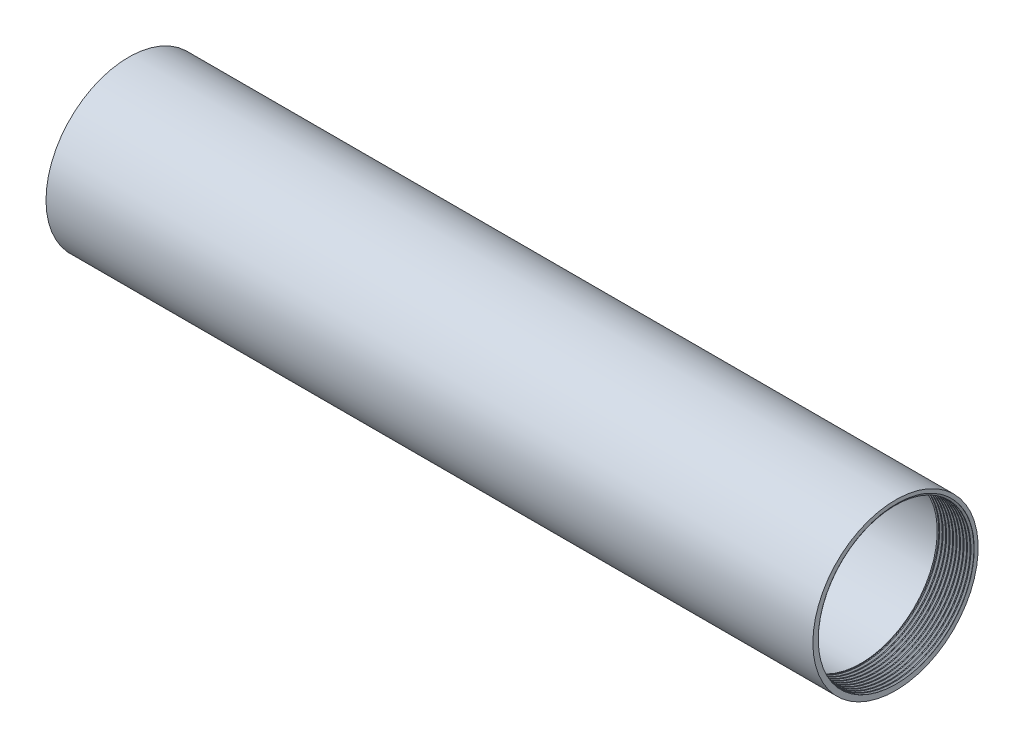
SolidWorks part; units mm, degrees
material "6061-T6 (SS)"
ref_plane "Front Plane" through (0, 0, 0) normal (0, 0, 1) x (1, 0, 0)
ref_plane "Top Plane" through (0, 0, 0) normal (0, 1, 0) x (1, 0, 0)
ref_plane "Right Plane" through (0, 0, 0) normal (1, 0, 0) x (0, 0, -1)
sketch "Sketch1" plane through (0, 0, 0) normal (0, 0, 1) x (1, 0, 0)
  line L0 (0, 37.719) -> (350.012, 37.719)
  line L1 (0, 0) -> (350.012, 0) construction
  line L2 (0, 37.719) -> (0, 35.2425)
  line L3 (0, 35.2425) -> (15.875, 35.2425)
  line L4 (15.875, 35.2425) -> (15.875, 34.925)
  line L5 (15.875, 34.925) -> (334.137, 34.925)
  line L6 (334.137, 34.925) -> (334.137, 35.2425)
  line L7 (334.137, 35.2425) -> (350.012, 35.2425)
  line L8 (350.012, 35.2425) -> (350.012, 37.719)
  point P6 (350.012, 36.4807)
  dimension "D1" = 350.012
  dimension "D2" = 34.925
  dimension "D3" = 37.719
  dimension "D4" = 35.2425
  dimension "D5" = 15.875
  dimension "D6" = 15.875
revolve "Revolve1" add sketch "Sketch1" angle 360 about L1
thread "Thread1" pitch 1.5875 method cut trim with start face yes trim with end face yes profile "Thread Profile1" start angle 0, offset 1.5875, length 0, pitch 1.5875, diameter 70.485
ref_plane "Plane1" through (17.4625, 0, 35.2425) normal (0, -1, 0) x (0, 0, 1)
sketch "Thread Profile1" plane through (17.4625, 0, 35.2425) normal (0, -1, 0) x (0, 0, 1)
  line L0 (0, 0) -> (0, 1.5875) construction
  line L1 (0, 0) -> (0.8593, 0.4961)
  line L2 (0.8593, 0.4961) -> (0.8593, 0.6945)
  line L3 (0.8593, 0.6945) -> (0, 1.1906)
  line L4 (0.8593, 0.5953) -> (0, 0.5953) construction
  line L11 (0, 0) -> (0, 1.1906)
  point P2 (0, 0)
  dimension "Pitch" = 1.5875
  dimension "Profile_Angle" = 60
  dimension "Profile_Land" = 0.1984
  dimension "Profile_Height" = 0.8593
thread "Thread2" pitch 1.5875 method cut trim with start face yes trim with end face yes profile "Thread Profile2" start angle 180, offset 1.5875, length 0, pitch 1.5875, diameter 70.485
ref_plane "Plane2" through (332.5495, 0, 35.2425) normal (0, 1, 0) x (0, 0, 1)
sketch "Thread Profile2" plane through (332.5495, 0, 35.2425) normal (0, 1, 0) x (0, 0, 1)
  line L0 (0, 0) -> (0, 1.5875) construction
  line L1 (0, 0) -> (0.8593, 0.4961)
  line L2 (0.8593, 0.4961) -> (0.8593, 0.6945)
  line L3 (0.8593, 0.6945) -> (0, 1.1906)
  line L4 (0.8593, 0.5953) -> (0, 0.5953) construction
  line L11 (0, 0) -> (0, 1.1906)
  point P2 (0, 0)
  dimension "Pitch" = 1.5875
  dimension "Profile_Angle" = 60
  dimension "Profile_Land" = 0.1984
  dimension "Profile_Height" = 0.8593
equation "\"D3@Sketch1\"=2.97/2"
equation "\"D6@Sketch1\"=\"D5@Sketch1\""
equation "\"D4@Sketch1\"=2.775/2"
equation "\"D2@Sketch1\"=2.75/2in"
